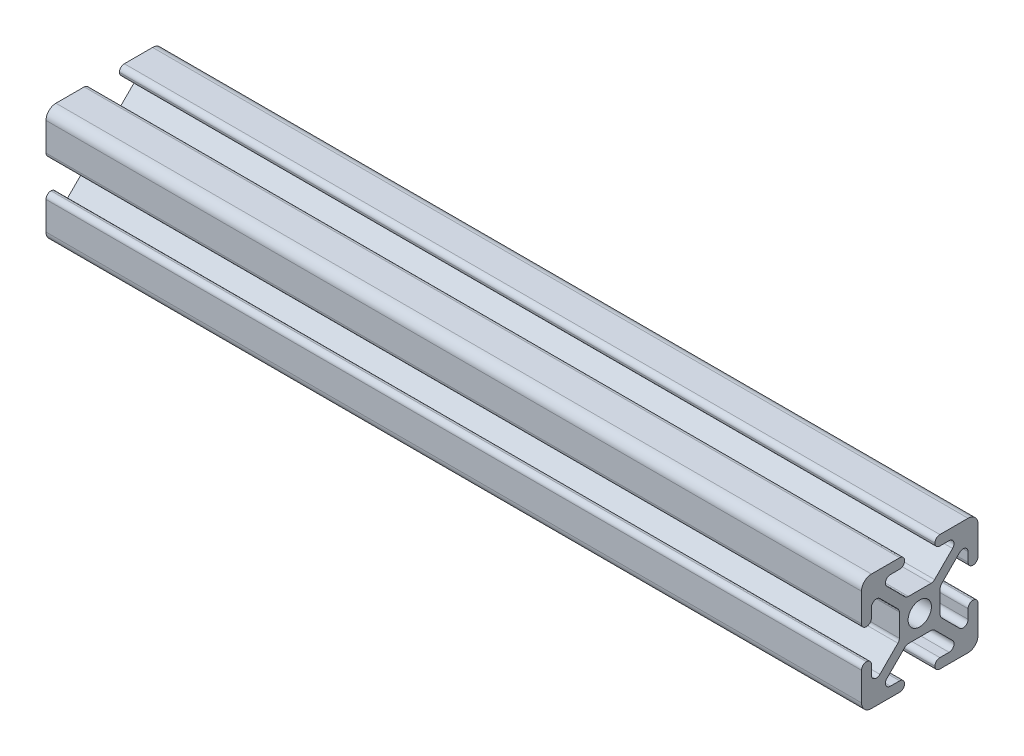
SolidWorks part; units mm, degrees
ref_plane "Front Plane" through (0, 0, 0) normal (1, 0, 0) x (0, 1, 0)
ref_plane "Top Plane" through (0, 0, 0) normal (0, 0, 1) x (0, 1, 0)
ref_plane "Right Plane" through (0, 0, 0) normal (0, 1, 0) x (-1, 0, 0)
sketch "Sketch1" plane through (0, 0, 0) normal (1, 0, 0) x (0, 1, 0)
  line L0 (0, 0) -> (0, 12.5) construction
  line L1 (-12.5, -12.5) -> (12.5, -12.5)
  line L2 (-12.5, -12.5) -> (-12.5, 12.5)
  line L3 (-12.5, 12.5) -> (12.5, 12.5)
  line L4 (12.5, -12.5) -> (12.5, 12.5)
  line L5 (-12.5, -12.5) -> (12.5, 12.5) construction
  line L6 (-12.5, 12.5) -> (12.5, -12.5) construction
  line L7 (-3.25, 12.5) -> (-3.25, 10.37)
  line L8 (-3.25, 10.37) -> (-8.8639, 10.37)
  line L9 (-8.8639, 10.37) -> (-2.8739, 4.38)
  line L10 (-2.8739, 4.38) -> (2.8739, 4.38)
  line L11 (8.8639, 10.37) -> (2.8739, 4.38)
  line L12 (3.25, 10.37) -> (8.8639, 10.37)
  line L13 (3.25, 12.5) -> (3.25, 10.37)
  line L14 (12.5, -3.25) -> (10.37, -3.25)
  line L15 (10.37, -3.25) -> (10.37, -8.8639)
  line L16 (10.37, -8.8639) -> (4.38, -2.8739)
  line L17 (4.38, 2.8739) -> (4.38, -2.8739)
  line L18 (10.37, 8.8639) -> (4.38, 2.8739)
  line L19 (10.37, 3.25) -> (10.37, 8.8639)
  line L20 (12.5, 3.25) -> (10.37, 3.25)
  line L21 (-3.25, -12.5) -> (-3.25, -10.37)
  line L22 (-3.25, -10.37) -> (-8.8639, -10.37)
  line L23 (-8.8639, -10.37) -> (-2.8739, -4.38)
  line L24 (2.8739, -4.38) -> (-2.8739, -4.38)
  line L25 (8.8639, -10.37) -> (2.8739, -4.38)
  line L26 (3.25, -10.37) -> (8.8639, -10.37)
  line L27 (3.25, -12.5) -> (3.25, -10.37)
  line L28 (-12.5, 3.25) -> (-10.37, 3.25)
  line L29 (-10.37, 3.25) -> (-10.37, 8.8639)
  line L30 (-10.37, 8.8639) -> (-4.38, 2.8739)
  line L31 (-4.38, -2.8739) -> (-4.38, 2.8739)
  line L32 (-10.37, -8.8639) -> (-4.38, -2.8739)
  line L33 (-10.37, -3.25) -> (-10.37, -8.8639)
  line L34 (-12.5, -3.25) -> (-10.37, -3.25)
  circle A0 centre (0, 0) radius 2.5
  point P0 (0, 0)
  point P15 (0, 4.38)
  dimension "D3" = 5
  dimension "D1" = 25
  dimension "D2" = 25
  dimension "D4" = 2.13
  dimension "D5" = 2.13
  dimension "D6" = 6.5
  dimension "D7" = 4.38
  dimension "D8" = 4
extrude "Boss-Extrude1" add sketch "Sketch1" along normal blind 175 contours L34 L2 L1 L21 L22 L23 L24 L25 L26 L27 L4 L14 L15 L16 L17 L18 L19 L20 L3 L13 L12 L11 L10 L9 L8 L7 L28 L29 L30 L31 L32 L33 A0 region at (0, -12.1464, -7.875)
fillet "Fillet1" radius 1.065 32 edges at (87.5, -10.37, -8.8639) (87.5, 2.8739, -4.38) (87.5, -2.8739, -4.38) (87.5, -4.38, 2.8739) (87.5, -4.38, -2.8739) (87.5, -2.8739, 4.38) (87.5, 2.8739, 4.38) (87.5, 4.38, 2.8739) (87.5, 4.38, -2.8739) (87.5, -8.8639, -10.37) (87.5, 8.8639, -10.37) (87.5, 10.37, -8.8639) (87.5, -10.37, 8.8639) (87.5, -8.8639, 10.37) (87.5, 10.37, 8.8639) (87.5, 8.8639, 10.37) (87.5, 12.5, 3.25) (87.5, -3.25, -12.5) (87.5, -10.37, 3.25) (87.5, 10.37, 3.25) (87.5, -10.37, -3.25) (87.5, -12.5, -3.25) (87.5, -12.5, 3.25) (87.5, 3.25, -10.37) (87.5, -3.25, -10.37) (87.5, 3.25, -12.5) (87.5, 10.37, -3.25) (87.5, 12.5, -3.25) (87.5, 3.25, 12.5) (87.5, 3.25, 10.37) (87.5, -3.25, 10.37) (87.5, -3.25, 12.5)
fillet "Fillet2" radius 2.13 4 edges at (87.5, 12.5, -12.5) (87.5, -12.5, -12.5) (87.5, 12.5, 12.5) (87.5, -12.5, 12.5)
